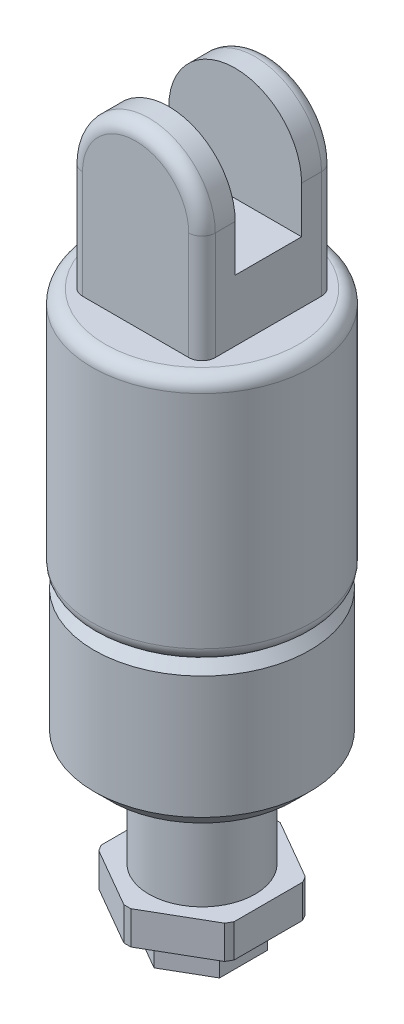
SolidWorks part; units mm, degrees
ref_plane "Front Plane" through (0, 0, 0) normal (0, 0, 1) x (1, 0, 0)
ref_plane "Top Plane" through (0, 0, 0) normal (0, 1, 0) x (1, 0, 0)
ref_plane "Right Plane" through (0, 0, 0) normal (1, 0, 0) x (0, 0, -1)
sketch "Sketch1" plane through (0, 0, 0) normal (0, 0, 1) x (1, 0, 0)
  line L0 (0, 0) -> (0, 36.8439) construction
  line L1 (6.5, 0) -> (6.5, 8.375)
  line L2 (6.5, 8.375) -> (6, 9)
  line L3 (6, 9) -> (6.625, 9.5)
  line L4 (6.625, 9.5) -> (6.625, 24)
  line L5 (6.625, 24) -> (0, 24)
  line L6 (6.5, 0) -> (0, 0)
  line L7 (0, 24) -> (0, 0)
  line L8 (6, 9) -> (0, 9) construction
  dimension "D1" = 13
  dimension "D2" = 9
  dimension "D3" = 15
  dimension "D4" = 13.25
  dimension "D5" = 6
revolve "revolve body" add sketch "Sketch1" angle 360 about L0
fillet "fillet round " radius 0.8 2 edges at (0, 24, -6.625) (0, 9.5, -6.625)
chamfer "chamf plastic base" distance 1 angle 45 1 edges at (0, 0, -6.5)
sketch "Sketch2" plane through (0, 0, 0) normal (0, 0, 1) x (1, 0, 0)
  line L0 (0, 0) -> (0, -21.5518) construction
  line L1 (3.2, 0) -> (3.2, -6)
  line L2 (-5.5, 0) -> (5.5, 0) construction
  line L3 (3.2, -6) -> (4.5, -6)
  line L4 (4.5, -6) -> (4.5, -8)
  line L5 (4.5, -8) -> (3.25, -8)
  line L6 (3.25, -8) -> (3.25, -10)
  line L7 (3.25, -10) -> (1.3, -10)
  line L8 (1.3, -10) -> (1.3, -15)
  line L9 (1.3, -15) -> (0, -15)
  line L10 (0, -15) -> (0, 0)
  line L11 (0, 0) -> (3.2, 0)
  point P7 (2.275, -10)
  dimension "D1" = 6.4
  dimension "D2" = 9
  dimension "D3" = 6.5
  dimension "D4" = 2.6
  dimension "D5" = 5
  dimension "D6" = 2
  dimension "D7" = 2
  dimension "D8" = 10
revolve "revolve threaded body" add sketch "Sketch2" angle 360 about L0
sketch "Sketch3" plane through (0, -8, 0) normal (0, -1, 0) x (1, 0, 0)
  line L1 (0, 4.6188) -> (-4, 2.3094)
  line L2 (-4, 2.3094) -> (-4, -2.3094)
  line L3 (-4, -2.3094) -> (0, -4.6188)
  line L4 (0, -4.6188) -> (4, -2.3094)
  line L5 (4, -2.3094) -> (4, 2.3094)
  line L6 (4, 2.3094) -> (0, 4.6188)
  circle A0 centre (0, 0) radius 4 construction
  dimension "D1" = 8
extrude "cut 8mm hex" cut sketch "Sketch3" against normal blind 3 flip side to cut
sketch "Sketch4" plane through (0, -10, 0) normal (0, -1, 0) x (1, 0, 0)
  line L1 (0, 2.8868) -> (-2.5, 1.4434)
  line L2 (-2.5, 1.4434) -> (-2.5, -1.4434)
  line L3 (-2.5, -1.4434) -> (0, -2.8868)
  line L4 (0, -2.8868) -> (2.5, -1.4434)
  line L5 (2.5, -1.4434) -> (2.5, 1.4434)
  line L6 (2.5, 1.4434) -> (0, 2.8868)
  circle A0 centre (0, 0) radius 2.5 construction
  dimension "D1" = 5
extrude "cut 5mm hex" cut sketch "Sketch4" against normal up to surface (2 mm away) flip side to cut up to face at (0, -8, 3.25)
sketch "Sketch5" plane through (0, 0, 0) normal (0, 0, 1) x (1, 0, 0)
  line L0 (5.825, 24) -> (-5.825, 24) construction
  line L1 (-4, 24) -> (4, 24)
  line L2 (-4, 24) -> (-4, 30.5)
  line L4 (4, 24) -> (4, 30.5)
  arc A0 (4, 30.5) -> (-4, 30.5) centre (0, 30.5) ccw
  dimension "D1" = 8
  dimension "D2" = 6.5
extrude "boss pivot" add sketch "Sketch5" along normal mid plane 8
fillet "fillet pivot" radius 0.8 6 edges at (4, 27.25, 4) (0, 34.5, 4) (4, 27.25, -4) (0, 34.5, -4) (-4, 27.25, 4) (-4, 27.25, -4)
ref_axis "PIVOT" through (0, 30.5, 3.2) along (0, 0, -1)
sketch "Sketch6" plane through (0, 0, 0) normal (1, 0, 0) x (0, 0, -1)
  line L0 (3.2, 34.5) -> (-3.2, 34.5) construction
  line L1 (-2, 34.5) -> (2, 34.5)
  line L2 (-2, 34.5) -> (-2, 27.7)
  line L3 (-2, 27.7) -> (2, 27.7)
  line L4 (2, 34.5) -> (2, 27.7)
  line L5 (-3.2, 24) -> (3.2, 24) construction
  point P8 (0, 27.7)
  dimension "D1" = 4
  dimension "D2" = 3.7
extrude "Cut-Extrude1" cut sketch "Sketch6" against normal through all both and the other way through all
sketch "Sketch7" plane through (0, -15, 0) normal (0, -1, 0) x (1, 0, 0)
  circle A1 centre (0, 0) radius 1.3
  circle A2 centre (0, 0) radius 1.3
  dimension "D1" = 0
extrude "Cut-Extrude2" cut sketch "Sketch7" against normal up to surface (5 mm away) up to face at (0, -10, 1.3)
